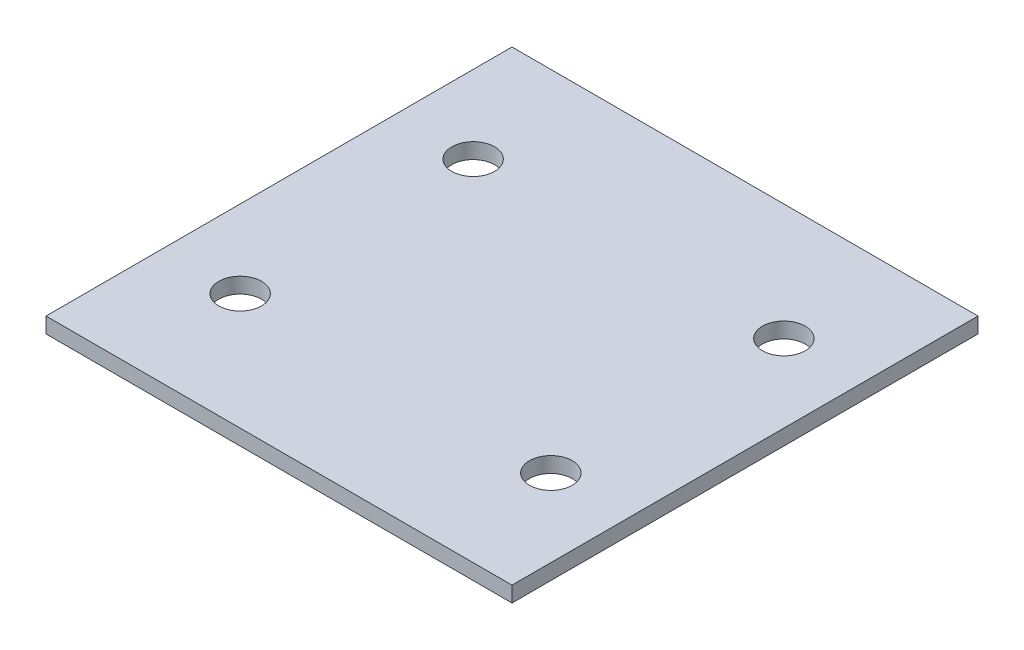
SolidWorks part; units mm, degrees
material "09Г2С ГОСТ 4543-71"
ref_plane "Спереди" through (0, 0, 0) normal (0, 0, 1) x (1, 0, 0)
ref_plane "Сверху" through (0, 0, 0) normal (0, 1, 0) x (1, 0, 0)
ref_plane "Справа" through (0, 0, 0) normal (1, 0, 0) x (0, 0, -1)
other "Configuration Table"
sketch "Эскиз1" plane through (0, 0, 0) normal (0, 1, 0) x (1, 0, 0)
  line L1 (-60, -60) -> (60, -60)
  line L2 (-60, -60) -> (-60, 60)
  line L3 (-60, 60) -> (60, 60)
  line L4 (60, -60) -> (60, 60)
  circle A0 centre (-40, -30) radius 5.5
  circle A1 centre (-40, 30) radius 5.5
  circle A2 centre (40, -30) radius 5.5
  circle A3 centre (40, 30) radius 5.5
extrude "Пластина 120х120х4, 4 отв. Ø11" add sketch "Эскиз1" along normal blind 4
